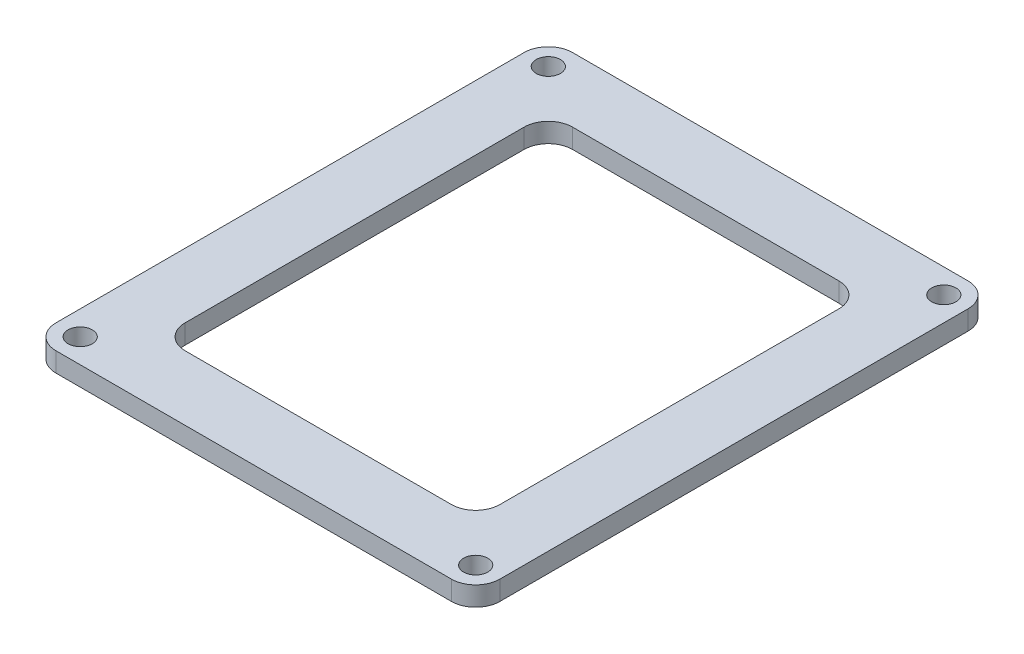
SolidWorks part; units mm, degrees
ref_plane "前视基准面" through (0, 0, 0) normal (0, 0, 1) x (1, 0, 0)
ref_plane "上视基准面" through (0, 0, 0) normal (0, 1, 0) x (1, 0, 0)
ref_plane "右视基准面" through (0, 0, 0) normal (1, 0, 0) x (0, 0, -1)
other "Configuration Table"
sketch "草图1" plane through (0, 0, 0) normal (0, 1, 0) x (1, 0, 0)
  line L0 (0, 46.8686) -> (0, -37.1951) construction
  line L1 (-27.5, -32) -> (27.5, -32)
  line L2 (-27.5, -32) -> (-27.5, 32)
  line L3 (-27.5, 32) -> (27.5, 32)
  line L4 (27.5, -32) -> (27.5, 32)
  line L5 (-27.5, -32) -> (27.5, 32) construction
  line L6 (-27.5, 32) -> (27.5, -32) construction
  line L7 (-32.226, 0) -> (32.7537, 0) construction
  line L8 (-19.5, -24) -> (-19.5, 24)
  line L9 (-19.5, 24) -> (19.5, 24)
  line L10 (19.5, -24) -> (19.5, 24)
  line L11 (-19.5, -24) -> (19.5, -24)
  circle A0 centre (-24.5, 29) radius 1.5
  circle A1 centre (24.5, 29) radius 1.5
  circle A2 centre (24.5, -29) radius 1.5
  circle A3 centre (-24.5, -29) radius 1.5
  point P0 (0, 0)
  dimension "D3" = 3
  dimension "D4" = 49
  dimension "D5" = 58
  dimension "D1" = 55
  dimension "D2" = 64
  dimension "D6" = 8
extrude "凸台-拉伸1" add sketch "草图1" along normal blind 2.4
fillet "圆角1" radius 3 8 edges at (-27.5, 1.2, -32) (27.5, 1.2, -32) (27.5, 1.2, 32) (-27.5, 1.2, 32) (-19.5, 1.2, 24) (19.5, 1.2, 24) (19.5, 1.2, -24) (-19.5, 1.2, -24)
